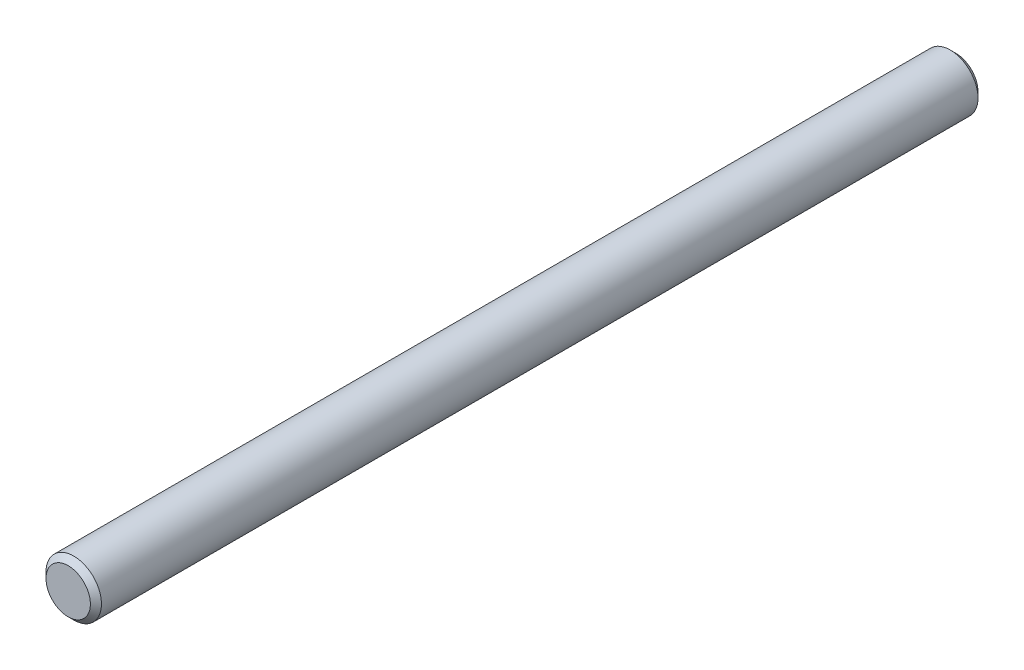
SolidWorks part; units mm, degrees
material "Plain Carbon Steel"
ref_plane "Front" through (0, 0, 0) normal (0, 0, 1) x (1, 0, 0)
ref_plane "Top" through (0, 0, 0) normal (0, 1, 0) x (1, 0, 0)
ref_plane "Right" through (0, 0, 0) normal (1, 0, 0) x (0, 0, -1)
sketch "Sketch1" plane through (0, 0, 0) normal (0, 0, 1) x (1, 0, 0)
  circle A0 centre (0, 0) radius 9.525
  dimension "dia" = 19.05
extrude "Extrude1" add sketch "Sketch1" along normal mid plane 304.8
sketch "Sketch2" plane through (0, 0, 0) normal (1, 0, 0) x (0, 0, -1)
  line L0 (152.4, 9.525) -> (149.86, 9.525) construction
  line L1 (152.4, 9.525) -> (-152.4, 9.525) construction
  line L2 (149.86, 9.525) -> (118.9037, 9.525) construction
  line L3 (118.9037, 9.525) -> (111.76, 9.525) construction
  line L4 (111.76, 9.525) -> (109.22, 9.525) construction
  line L5 (109.22, 9.525) -> (106.5632, 9.525) construction
  line L7 (100.2132, 9.525) -> (95.4507, 9.525) construction
  line L8 (95.4507, 9.525) -> (84.0207, 9.525) construction
  line L10 (-152.4, -9.525) -> (152.4, -9.525) construction
  line L11 (-152.4, 9.525) -> (-149.86, 9.525) construction
  line L12 (-149.86, 9.525) -> (-149.86, -9.525) construction
  line L13 (106.5632, 9.525) -> (100.2132, 9.525) construction
  line L14 (100.2132, 9.525) -> (100.2132, -9.525) construction
  line L15 (111.76, 9.525) -> (111.76, -9.525) construction
  line L16 (84.0207, 9.525) -> (79.2582, 9.525) construction
  line L17 (79.2582, 9.525) -> (67.8282, 9.525) construction
  line L18 (67.8282, 9.525) -> (63.0657, 9.525) construction
  line L19 (63.0657, 9.525) -> (51.6357, 9.525) construction
  line L20 (84.0207, 9.525) -> (84.0207, -9.525) construction
  line L21 (67.8282, 9.525) -> (67.8282, -9.525) construction
  line L22 (51.6357, 9.525) -> (51.6357, -9.525) construction
  line L23 (51.6357, 9.525) -> (46.8732, 9.525) construction
  line L24 (46.8732, 9.525) -> (35.4432, 9.525) construction
  line L25 (35.4432, 9.525) -> (35.4432, -9.525) construction
  line L26 (35.4432, 9.525) -> (30.6807, 9.525) construction
  line L27 (30.6807, 9.525) -> (19.2507, 9.525) construction
  line L28 (19.2507, 9.525) -> (14.4882, 9.525) construction
  line L29 (14.4882, 9.525) -> (3.0582, 9.525) construction
  line L30 (19.2507, 9.525) -> (19.2507, -9.525) construction
  line L31 (3.0582, 9.525) -> (3.0582, -9.525) construction
  line L32 (3.0582, 9.525) -> (-1.7043, 9.525) construction
  line L33 (-1.7043, 9.525) -> (-8.0543, 9.525) construction
  line L34 (-8.0543, 9.525) -> (-10.7112, 9.525) construction
  line L35 (-10.7112, 9.525) -> (-13.2512, 9.525) construction
  line L36 (-13.2512, 9.525) -> (-13.2512, -9.525) construction
  line L37 (-13.2512, 9.525) -> (-64.0512, 9.525) construction
  line L38 (-64.0512, 9.525) -> (-64.0512, -9.525) construction
  point P0 (-152.4, 9.525)
  point P1 (152.4, 9.525)
  dimension "D1" = 2.54
  dimension "D2" = 30.9562
  dimension "D3" = 7.1437
  dimension "D4" = 2.54
  dimension "D5" = 2.6568
  dimension "D6" = 6.35
  dimension "D7" = 11.43
  dimension "D8" = 2.54
  dimension "D9" = 4.7625
  dimension "D10" = 4.7625
  dimension "D11" = 11.43
  dimension "D12" = 4.7625
  dimension "D13" = 11.43
  dimension "D14" = 4.7625
  dimension "D15" = 11.43
  dimension "D16" = 4.7625
  dimension "D17" = 11.43
  dimension "D18" = 4.7625
  dimension "D19" = 11.43
  dimension "D20" = 4.7625
  dimension "D21" = 6.35
  dimension "D22" = 2.6568
  dimension "D23" = 2.54
  dimension "D24" = 50.8
chamfer "Chamfer1" distance 1.905 angle 45 2 edges at (9.525, 0, -152.4) (9.525, 0, 152.4)
equation "\"D1@Chamfer1\" = \"dia@Sketch1\" * .1"
